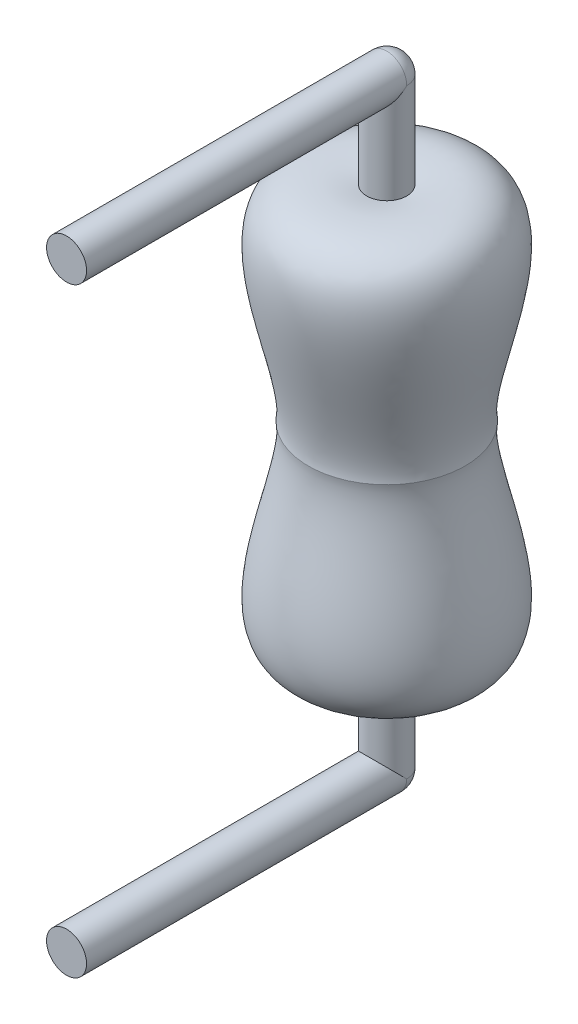
SolidWorks part; units mm, degrees
ref_plane "Plan de face" through (0, 0, 0) normal (0, 0, 1) x (1, 0, 0)
ref_plane "Plan de dessus" through (0, 0, 0) normal (0, 1, 0) x (1, 0, 0)
ref_plane "Plan de droite" through (0, 0, 0) normal (1, 0, 0) x (0, 0, -1)
sketch "Esquisse2" plane through (0, 0, 0) normal (0, 0, 1) x (1, 0, 0)
  line L0 (0, 0) -> (0, 5) construction
  line L1 (-0.9792, 2.5) -> (0, 2.5)
  line L2 (0, 0) -> (0, 5)
  line L3 (0, 2.5) -> (-4.4028, 2.5) construction
  line L5 (0, 5) -> (-0.25, 5)
  line L6 (0, 5) -> (0, 6.25)
  line L7 (0, 6.25) -> (-0.25, 6.25)
  line L8 (-0.25, 5) -> (-0.25, 6.25)
  line L9 (0, 0) -> (-0.25, 0)
  line L10 (0, 0) -> (0, -1.25)
  line L11 (0, -1.25) -> (-0.25, -1.25)
  line L12 (-0.25, 0) -> (-0.25, -1.25)
  spline S0 degree 3 poles (0, 5) (-2.2138, 5.5869) (-0.8565, 3.2668) (-0.9792, 2.5) knots 0 0 0 0 1 1 1 1
  spline S1 degree 3 poles (0, 0) (-2.2138, -0.5869) (-0.8565, 1.7332) (-0.9792, 2.5) knots 0 0 0 0 1 1 1 1
  dimension "D1" = 0.25
  dimension "D2" = 2.5
  dimension "D3" = 1.25
  dimension "D4" = 0.25
  dimension "D5" = 1.25
revolve "Révolution1" add sketch "Esquisse2" angle 360 about L2 region at (-0.5776, 3.829, 0) region at (-0.5776, 1.171, 0) region at (-0.1645, 5.0196, 0) region at (-0.124, 5.64, 0) region at (-0.124, -0.64, 0) region at (-0.1645, -0.0196, 0)
sketch "Esquisse4" plane through (0, -1.25, 0) normal (0, -1, 0) x (-1, 0, 0)
  line L0 (0, 0) -> (0, -4) construction
  line L2 (0, 0.25) -> (-0.25, 0.25)
  line L3 (0, 0.25) -> (0, -4)
  line L4 (0, -4) -> (-0.25, -4)
  line L5 (-0.25, 0.25) -> (-0.25, -4)
  circle A0 centre (0, 0) radius 0.25 construction
  circle A1 centre (0, 0) radius 0.25 construction
  circle A2 centre (0, 0) radius 0.25
  dimension "D1" = 4
  dimension "D2" = 0.25
revolve "Révolution2" add sketch "Esquisse4" angle 360 about L0 region at (0.1061, -1.25, 0) region at (0.126, -1.25, 2.0978)
sketch "Esquisse5" plane through (0, 6.25, 0) normal (0, 1, 0) x (1, 0, 0)
  line L0 (0, 0) -> (0, 0.25)
  line L1 (0, 0) -> (-0.25, 0)
  line L2 (0, 0) -> (0, -4)
  line L3 (0, -4) -> (-0.25, -4)
  line L4 (-0.25, 0) -> (-0.25, -4)
  circle A0 centre (0, 0) radius 0.25
  dimension "D1" = 4
  dimension "D2" = 0.25
revolve "Révolution3" add sketch "Esquisse5" angle 360 about L2 region at (-0.1061, 6.25, -0.1061) region at (-0.1061, 6.25, 0.1061) region at (-0.126, 6.25, 2.0978)
